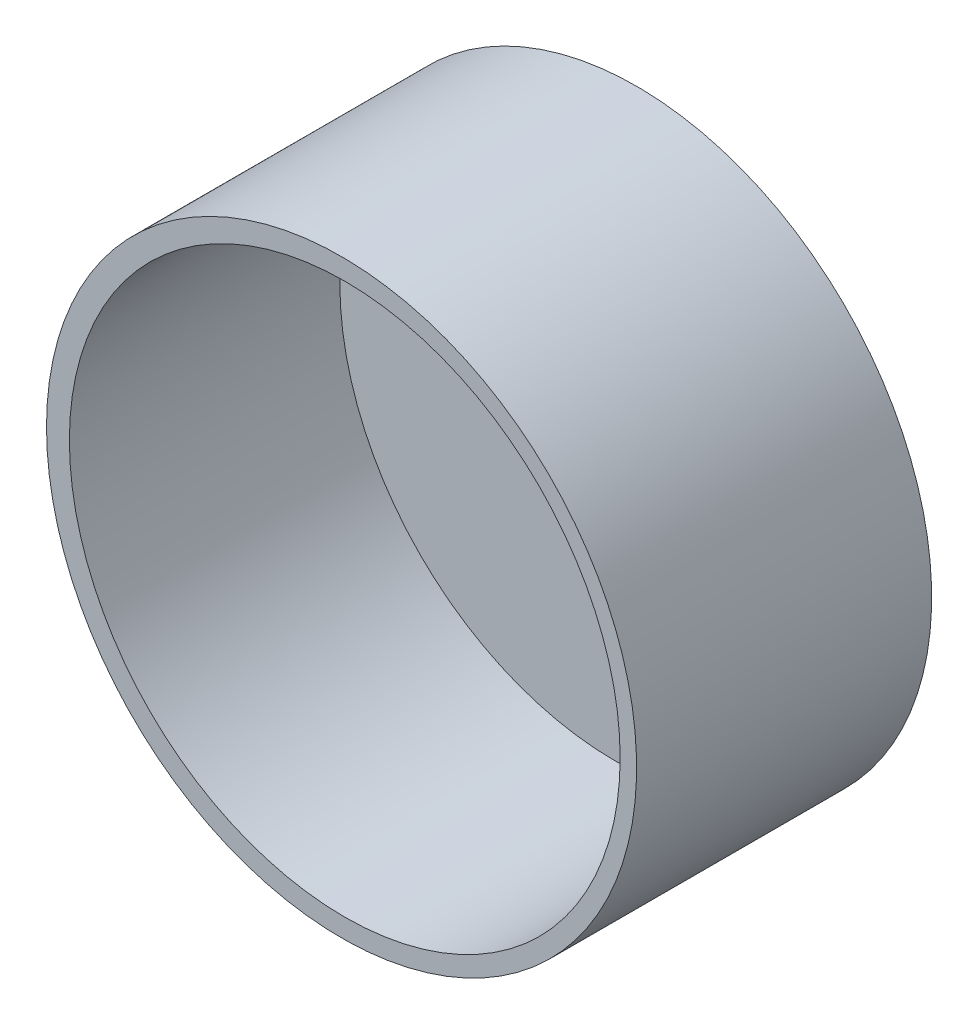
SolidWorks part; units mm, degrees
material "AISI 1020"
ref_plane "Front Plane" through (0, 0, 0) normal (0, 0, 1) x (1, 0, 0)
ref_plane "Top Plane" through (0, 0, 0) normal (0, 1, 0) x (1, 0, 0)
ref_plane "Right Plane" through (0, 0, 0) normal (1, 0, 0) x (0, 0, -1)
sketch "Sketch1" plane through (0, 0, 0) normal (0, 0, 1) x (1, 0, 0)
  circle A0 centre (0, 0) radius 76.2
  circle A1 centre (0.8288, 0) radius 71.12
  dimension "D1" = 152.4
  dimension "D2" = 142.24
extrude "Boss-Extrude1" add sketch "Sketch1" along normal blind 76.2
sketch "Sketch3" plane through (0, 0, 0) normal (0, 0, 1) x (1, 0, 0)
  circle A0 centre (0, 0) radius 76.2
extrude "Boss-Extrude2" add sketch "Sketch3" along normal blind 6.35
sketch "Sketch4" plane through (0, 0, 6.35) normal (0, 0, 1) x (1, 0, 0)
  circle A0 centre (0, 0) radius 19.05
  dimension "D1" = 38.1
extrude "Cut-Extrude1" cut sketch "Sketch4" against normal blind 2.54
